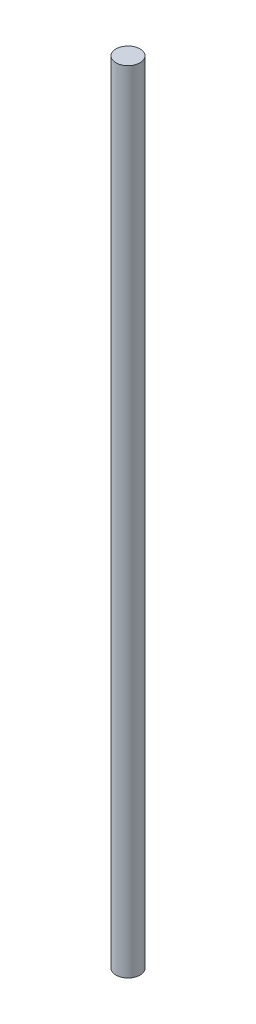
SolidWorks part; units mm, degrees
ref_plane "Front Plane" through (0, 0, 0) normal (0, 0, 1) x (1, 0, 0)
ref_plane "Top Plane" through (0, 0, 0) normal (0, 1, 0) x (1, 0, 0)
ref_plane "Right Plane" through (0, 0, 0) normal (1, 0, 0) x (0, 0, -1)
sketch "Sketch1" plane through (0, 0, 0) normal (0, 1, 0) x (1, 0, 0)
  circle A0 centre (0, 0) radius 76.2
  dimension "D1" = 152.4
extrude "Boss-Extrude1" add sketch "Sketch1" along normal blind 5000
